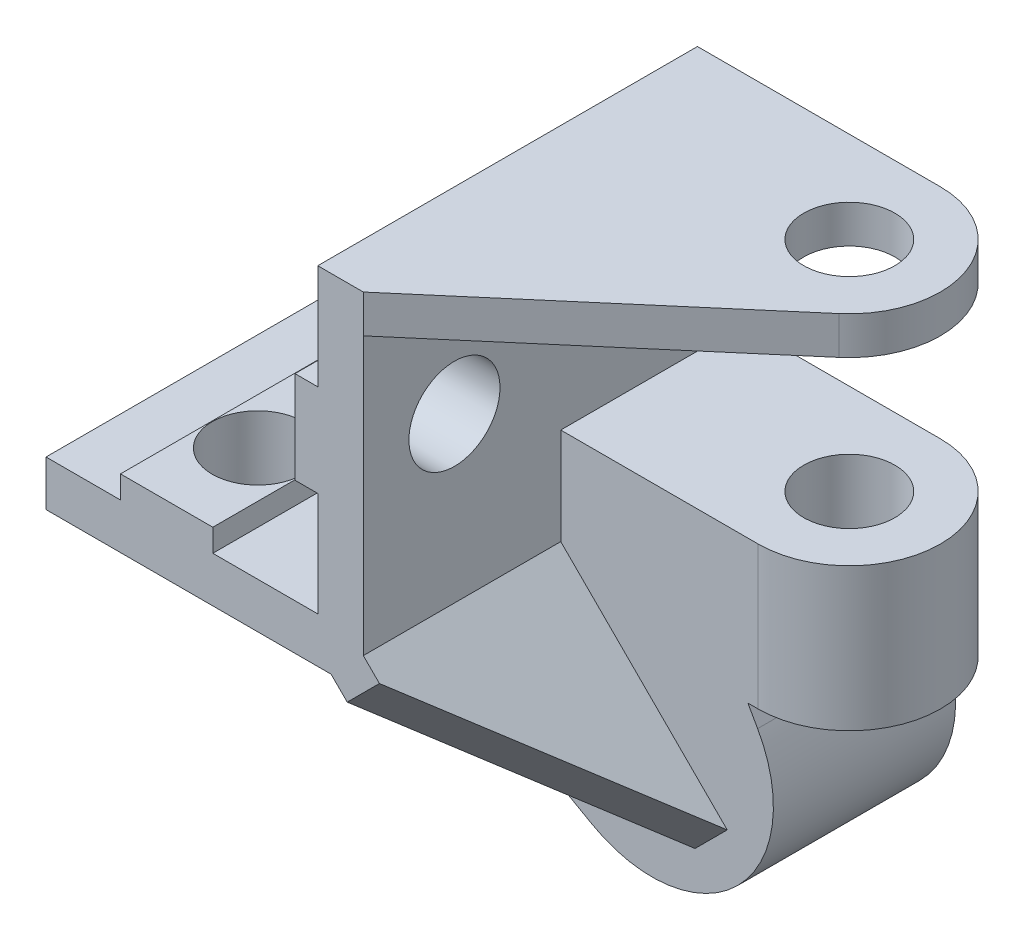
SolidWorks part; units mm, degrees
material "ABS"
ref_plane "Front Plane" through (0, 0, 0) normal (0, 0, 1) x (1, 0, 0)
ref_plane "Top Plane" through (0, 0, 0) normal (0, 1, 0) x (1, 0, 0)
ref_plane "Right Plane" through (0, 0, 0) normal (1, 0, 0) x (0, 0, -1)
sketch "Sketch1" plane through (0, 0, 0) normal (0, 0, 1) x (1, 0, 0)
  line L0 (227.0887, 62.283) -> (227.0887, 57.3796)
  line L1 (227.0887, 44.4296) -> (220.1787, 44.4296)
  line L2 (209.1953, 44.4296) -> (209.1953, 41.4296)
  line L3 (209.1953, 41.4296) -> (230.0887, 41.4296)
  line L4 (230.0887, 41.4296) -> (230.0887, 62.283)
  line L5 (230.0887, 62.283) -> (227.0887, 62.283)
  line L6 (214.0987, 45.9172) -> (214.0987, 44.4296)
  line L7 (220.1787, 45.9172) -> (220.1787, 44.4296)
  line L8 (220.1787, 45.9172) -> (214.0987, 45.9172)
  line L9 (225.5901, 57.3796) -> (227.0887, 57.3796)
  line L10 (225.5901, 51.2996) -> (227.0887, 51.2996)
  line L11 (225.5901, 51.2996) -> (225.5901, 57.3796)
  line L12 (227.0887, 51.2996) -> (227.0887, 44.4296)
  line L13 (214.0987, 44.4296) -> (209.1953, 44.4296)
  dimension "D1" = 17.8534
  dimension "D2" = 17.8934
  dimension "D3" = 1.4876
  dimension "D4" = 4.9034
  dimension "D5" = 4.9034
  dimension "D6" = 6.08
  dimension "D7" = 1.4986
  dimension "D8" = 3
extrude "Boss-Extrude1" add sketch "Sketch1" against normal blind 25
sketch3d "3DSketch1"
  line L0 (225.5901, 54.3396, 0) -> (230.0887, 54.3396, 0) construction
  line L1 (225.5901, 57.3796, 0) -> (225.5901, 51.2996, 0) construction
  line L2 (230.0887, 41.4296, 0) -> (230.0887, 62.283, 0) construction
  line L3 (230.0887, 54.3396, 0) -> (230.0887, 54.3396, -25) construction
  line L4 (230.0887, 41.4296, -25) -> (230.0887, 62.283, -25) construction
  line L5 (217.1387, 45.9172, 0) -> (217.1387, 41.4296, 0) construction
  line L6 (220.1787, 45.9172, 0) -> (214.0987, 45.9172, 0) construction
  line L7 (209.1953, 41.4296, 0) -> (230.0887, 41.4296, 0) construction
  line L8 (217.1387, 41.4296, 0) -> (217.1387, 41.4296, -25) construction
  line L9 (209.1953, 41.4296, -25) -> (230.0887, 41.4296, -25) construction
sketch "Sketch2" plane through (230.0887, 0, 0) normal (1, 0, 0) x (0, 0, -1)
  circle A0 centre (6, 54.3396) radius 3
  dimension "D1" = 6
  dimension "D2" = 6
extrude "Cut-Extrude1" cut sketch "Sketch2" against normal blind 15
sketch "Sketch3" plane through (0, 41.4296, 0) normal (0, -1, 0) x (1, 0, 0)
  circle A0 centre (217.1387, -6) radius 3
  dimension "D1" = 6
  dimension "D2" = 6
extrude "Cut-Extrude2" cut sketch "Sketch3" against normal blind 15
sketch "Sketch4" plane through (0, 0, -25) normal (0, 0, -1) x (-1, 0, 0)
  line L0 (-237.9258, 48.4296) -> (-243.0517, 39.3686)
  line L2 (-232.1548, 28.4636) -> (-209.1953, 41.4296)
  line L3 (-209.1953, 41.4296) -> (-230.0887, 41.4296) construction
  line L4 (-209.1953, 44.4296) -> (-209.1953, 41.4296) construction
  line L5 (-209.1953, 41.4296) -> (-230.0887, 41.4296)
  line L6 (-230.0887, 41.4296) -> (-230.0887, 48.4296)
  line L7 (-237.9258, 48.4296) -> (-230.0887, 48.4296)
  line L8 (-230.0887, 41.4296) -> (-230.0887, 62.283) construction
  arc A0 (-243.0517, 39.3686) -> (-232.1548, 28.4636) centre (-236.0887, 35.4296) ccw
  dimension "D3" = 8
  dimension "D1" = 6
  dimension "D2" = 6
  dimension "D4" = 7
extrude "Boss-Extrude2" add sketch "Sketch4" against normal blind 12
ref_plane "Plane1" through (135.7174, 135.7666, 0) normal (-0.707, -0.7072, 0) x (0.7072, -0.707, 0)
sketch "Sketch5" plane through (135.7174, 135.7666, 0) normal (-0.707, -0.7072, 0) x (0.7072, -0.707, 0)
  line L1 (133.437, -13) -> (133.437, 0) construction
  line L2 (133.437, -13) -> (147.437, -13)
  line L3 (147.437, -13) -> (133.437, 0)
  line L4 (133.437, 0) -> (129.1944, 0)
  line L5 (129.1944, 0) -> (129.1944, -13)
  line L6 (129.1944, -13) -> (133.437, -13)
  dimension "D1" = 14
extrude "Boss-Extrude4" add sketch "Sketch5" along normal mid plane 3
sketch "Sketch6" plane through (0, 0, -25) normal (0, 0, -1) x (-1, 0, 0)
  circle A1 centre (-236.0887, 35.4296) radius 4.85
  arc A2 (-243.0517, 39.3686) -> (-232.1548, 28.4636) centre (-236.0887, 35.4296) ccw construction
  dimension "D1" = 9.7
extrude "Cut-Extrude3" cut sketch "Sketch6" against normal blind 9
sketch "Sketch8" plane through (0, 62.283, 0) normal (0, 1, 0) x (-1, 0, 0)
  line L0 (-230.0887, -25) -> (-227.0887, -25) construction
  line L1 (-227.0887, -25) -> (-243.0887, -25)
  line L2 (-227.0887, -25) -> (-227.0887, -13)
  line L3 (-227.0887, -13) -> (-243.0887, -13)
  line L4 (-243.0887, -25) -> (-243.0887, -13) construction
  line L5 (-227.0887, -25) -> (-227.0887, 0) construction
  arc A0 (-243.0887, -13) -> (-243.0887, -25) centre (-243.0887, -19) ccw
  dimension "D1" = 12
  dimension "D2" = 16
extrude "Boss-Extrude5" add sketch "Sketch8" along normal blind 2 and the other way blind 0.5
extrude "Boss-Extrude6" add sketch "Sketch8<2>" against normal blind 9.4087 from offset 12.37 offset against normal yes
sketch "Sketch8<2>" plane through (0, 62.283, 0) normal (0, 1, 0) x (-1, 0, 0) same geometry as "Sketch8"
sketch "Sketch9" plane through (0, 64.283, 0) normal (0, 1, 0) x (-1, 0, 0)
  line L0 (-227.0887, -13) -> (-227.0887, 0)
  line L1 (-227.0887, -13) -> (-243.0887, -13) construction
  line L2 (-227.0887, 0) -> (-230.0887, 0)
  line L3 (-230.0887, 0) -> (-246.9864, -14.4384)
  line L4 (-227.0887, -13) -> (-243.0887, -13)
  arc A0 (-243.0887, -13) -> (-243.0887, -25) centre (-243.0887, -19) ccw construction
  arc A1 (-243.0887, -13) -> (-246.9864, -14.4384) centre (-243.0887, -19) ccw
extrude "Boss-Extrude7" add sketch "Sketch9" against normal blind 2.5
sketch "Sketch10" plane through (0, 64.283, 0) normal (0, 1, 0) x (-1, 0, 0)
  circle A0 centre (-243.0887, -19) radius 3
  arc A1 (-246.9864, -14.4384) -> (-243.0887, -25) centre (-243.0887, -19) ccw construction
  dimension "D1" = 6
extrude "Cut-Extrude4" cut sketch "Sketch10" against normal blind 21
